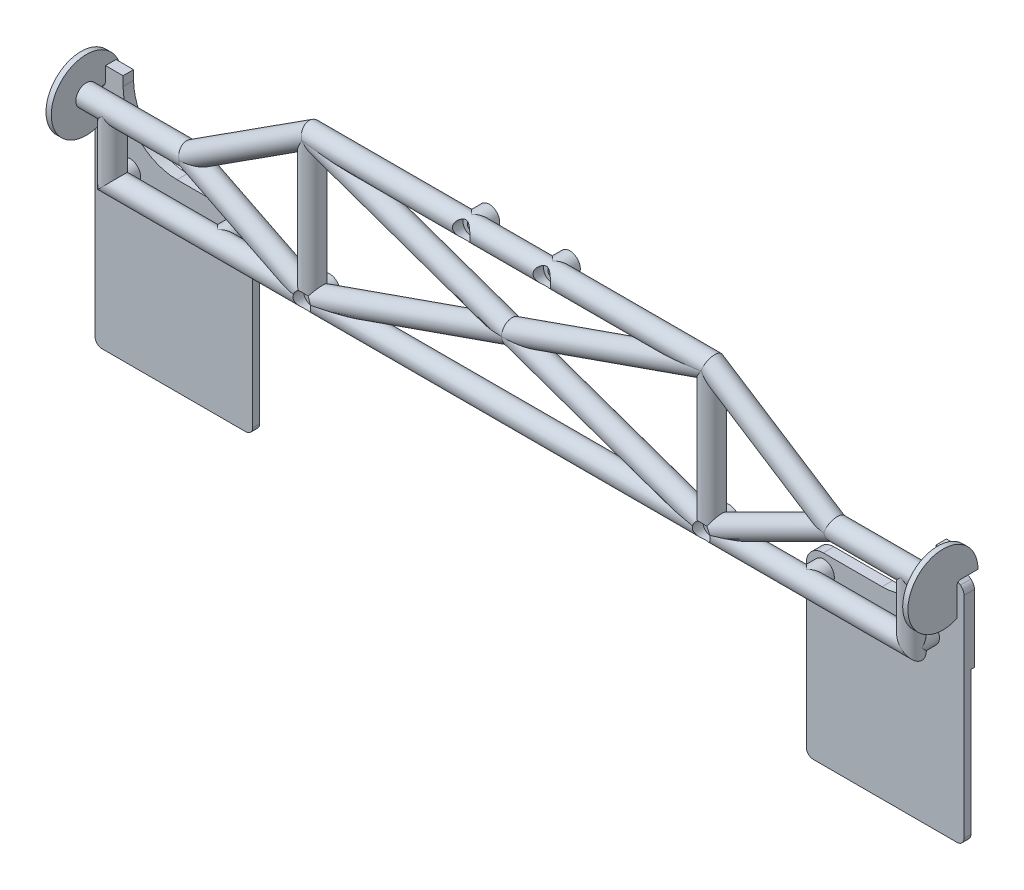
SolidWorks part; units mm, degrees
ref_plane "Front Plane" through (0, 0, 0) normal (0, 0, 1) x (1, 0, 0)
ref_plane "Top Plane" through (0, 0, 0) normal (0, 1, 0) x (1, 0, 0)
ref_plane "Right Plane" through (0, 0, 0) normal (1, 0, 0) x (0, 0, -1)
sketch "Sketch1" plane through (0, 0, 0) normal (0, 0, 1) x (1, 0, 0)
  line L0 (57, 20) -> (92, -2.5)
  line L1 (92, -2.5) -> (121.5, -2.5)
  line L2 (0, 0) -> (0, 9.1731) construction
  line L3 (57, 20) -> (-57, 20)
  line L5 (57, -20) -> (-57, 20) construction
  line L6 (57, 20) -> (-57, -20) construction
  line L7 (-92, -2.5) -> (-121.5, -2.5)
  line L8 (-57, 20) -> (-92, -2.5)
  point P0 (0, 0)
  dimension "D1" = 114
  dimension "D2" = 40
  dimension "D3" = 22.5
  dimension "D4" = 35
  dimension "D5" = 121.5
sweep "Sweep1" add path "Sketch1" circular profile diameter 6 parameters "D3"=6
sketch "Sketch108" plane through (0, 0, 0) normal (0, 0, 1) x (1, 0, 0)
  line L0 (-121.5, -2.5) -> (-92, -2.5)
  line L1 (-121.5, 0.5) -> (-121.5, -5.5) construction
  line L2 (-91.1189, -5.5) -> (-92.8811, 0.5) construction
  line L3 (-92, -2.5) -> (-57, -20)
  line L4 (-57, -20) -> (57, -20)
  line L5 (57, -20) -> (92, -2.5)
  line L6 (91.1189, -5.5) -> (92.8811, 0.5) construction
  line L7 (92, -2.5) -> (121.5, -2.5)
  line L8 (121.5, -5.5) -> (121.5, 0.5) construction
  line L9 (57, -20) -> (57, 20) construction
  line L10 (57.8811, 23) -> (56.1189, 17) construction
  line L11 (-57, 20) -> (-57, -20) construction
  line L12 (-57.8811, 23) -> (-56.1189, 17) construction
  dimension "D1" = 40
sweep "Sweep6" add path "Sketch108" circular profile diameter 6 parameters "D3"=6
sketch "Sketch121" plane through (0, 0, 0) normal (0, 0, 1) x (1, 0, 0)
  line L0 (-57, 20) -> (57, -20)
  line L1 (-57.8811, 23) -> (-56.1189, 17) construction
  line L2 (57.7082, -23) -> (56.2918, -17) construction
sweep "Sweep7" add path "Sketch121" circular profile diameter 6 parameters "D3"=6
sketch "Sketch130" plane through (0, 0, 0) normal (0, 0, 1) x (1, 0, 0)
  line L0 (-57, -20) -> (57, 20)
  line L1 (-57.7082, -23) -> (-56.2918, -17) construction
  line L2 (57.8811, 23) -> (56.1189, 17) construction
sweep "Sweep8" add path "Sketch130" circular profile diameter 6 parameters "D3"=6
sketch "Sketch143" plane through (0, 0, 0) normal (0, 0, 1) x (1, 0, 0)
  line L0 (-57, 20) -> (-57, -20)
sweep "Sweep9" add path "Sketch143" circular profile diameter 6 parameters "D3"=6
sketch "Sketch152" plane through (0, 0, 0) normal (0, 0, 1) x (1, 0, 0)
  line L0 (57, 20) -> (57, -20)
sweep "Sweep10" add path "Sketch152" circular profile diameter 6 parameters "D3"=6
sketch "Sketch165" plane through (0, 0, 0) normal (0, 0, 1) x (1, 0, 0)
  line L0 (57, -20) -> (114, -20)
  line L1 (114, -20) -> (114, -2.5)
  line L2 (121.5, -2.5) -> (116.1969, -2.5) construction
  line L3 (121.5, -5.5) -> (121.5, 0.5) construction
  dimension "D1" = 57
sweep "Sweep11" add path "Sketch165" circular profile diameter 6 parameters "D3"=6
mirror "Mirror1" about plane through (0, 0, 0) normal (1, 0, 0) of "Sweep11"
sketch "Sketch182" plane through (0, 0, 0) normal (0, 0, 1) x (1, 0, 0)
  line L0 (-8.5, 20) -> (8.5, 20) construction
  line L1 (0, 20) -> (0, 0) construction
  line L2 (117, -23) -> (111, -17) construction
  line L3 (114, -20) -> (111.8989, -20) construction
  line L4 (-117, -23) -> (-111, -17) construction
  line L5 (-114, -20) -> (-111.7577, -20) construction
  circle A0 centre (11.5, 20) radius 3
  circle A1 centre (-11.5, 20) radius 3
  circle A2 centre (57, -20) radius 3
  circle A3 centre (-57, -20) radius 3
  circle A4 centre (114, -20) radius 3
  circle A5 centre (84, -20) radius 3
  circle A6 centre (-114, -20) radius 3
  circle A7 centre (-84, -20) radius 3
  dimension "D2" = 6
  dimension "D3" = 6
  dimension "D4" = 6
  dimension "D5" = 6
  dimension "D6" = 6
  dimension "D7" = 6
  dimension "D9" = 6
  dimension "D10" = 6
  dimension "D1" = 17
  dimension "D8" = 30
  dimension "D11" = 30
extrude "Boss-Extrude1" add sketch "Sketch182" against normal blind 5
sketch "Sketch183" plane through (0, 0, 0) normal (0, 0, 1) x (1, 0, 0)
  circle A0 centre (11.5, 20) radius 2.5
  circle A1 centre (-11.5, 20) radius 2.5
  circle A2 centre (57, -20) radius 2.5
  circle A3 centre (-57, -20) radius 2.5
  circle A4 centre (-57, -20) radius 3 construction
  circle A6 centre (-11.5, 20) radius 3 construction
  circle A7 centre (11.5, 20) radius 3 construction
  circle A8 centre (57, -20) radius 3 construction
  dimension "D1" = 5
  dimension "D2" = 5
  dimension "D3" = 5
  dimension "D4" = 5
extrude "Cut-Extrude1" cut sketch "Sketch183" along normal blind 5
sketch "Sketch184" plane through (0, 0, -5) normal (0, 0, -1) x (-1, 0, 0)
  circle A0 centre (-11.5, 20) radius 1.25
  circle A1 centre (11.5, 20) radius 1.25
  circle A2 centre (57, -20) radius 1.25
  circle A3 centre (-57, -20) radius 1.25
  dimension "D1" = 2.5
  dimension "D2" = 2.5
  dimension "D3" = 2.5
  dimension "D4" = 2.5
extrude "Cut-Extrude2" cut sketch "Sketch184" against normal through all
ref_axis "Axis1" through (-11.5, 20, 0) along (0, 0, -1)
ref_axis "Axis2" through (11.5, 20, 0) along (0, 0, -1)
ref_plane "Plane1" through (0, 20, 0) normal (0, -1, 0) x (-1, 0, 0)
sketch "Sketch201" plane through (121.5, 0, 0) normal (1, 0, 0) x (0, 0, -1)
  line L0 (10, -2.5) -> (5, -2.5)
  line L1 (4, -3.5) -> (4, -11.6652)
  circle A0 centre (0, -2.5) radius 10
  circle A1 centre (0, -2.5) radius 3 construction
  arc A2 (4, -3.5) -> (5, -2.5) centre (5, -3.5) cw
  point P9 (4, -2.5)
  circle M2 centre (0, -2.5) radius 3
  dimension "D1" = 20
  dimension "D3" = 1
  dimension "D2" = 6
extrude "Boss-Extrude2" add sketch "Sketch201" along normal blind 1.5 separate body contours L1 A2 L0 A0 M2 | M2 region at (121.5, -2.2172, -7.5) region at (121.5, -2.5, 0)
mirror "Mirror3" about plane through (0, 0, 0) normal (1, 0, 0) of "Boss-Extrude2"
sketch "Sketch202" plane through (0, 0, -5) normal (0, 0, -1) x (-1, 0, 0)
  line L0 (124, -66) -> (124, -5.9498)
  line L1 (123, -3.5) -> (123, -11.6652) construction
  line L2 (122.967, -3.9255) -> (122.033, -3.2486)
  line L3 (121, -1.2243) -> (121, 2.5)
  line L4 (121, 2.5) -> (116, 2.5)
  line L5 (116, 2.5) -> (116, -0.1131)
  line L6 (100.6131, -15.5) -> (83.865, -15.5)
  line L7 (79, -20.365) -> (79, -66)
  line L8 (122, -68) -> (81, -68)
  line L9 (111, -17) -> (84, -17) construction
  arc A0 (116, -0.1131) -> (100.6131, -15.5) centre (100.6131, -0.1131) cw
  arc A1 (83.865, -15.5) -> (79, -20.365) centre (83.865, -20.365) ccw
  arc A2 (122.967, -3.9255) -> (124, -5.9498) centre (121.5, -5.9498) cw
  arc A3 (122.033, -3.2486) -> (121, -1.2243) centre (123.5, -1.2243) cw
  arc A4 (124, -66) -> (122, -68) centre (122, -66) cw
  arc A5 (81, -68) -> (79, -66) centre (81, -66) cw
  point P13 (80.2038, -64.3084)
  point P17 (124, -4.6741)
  point P22 (121, -2.5)
  point P23 (116, -0.1131)
  point P24 (83.865, -15.5)
  dimension "D9" = 2.5
  dimension "D10" = 2
  dimension "D1" = 1
  dimension "D2" = 45
  dimension "D3" = 52.5
  dimension "D4" = 18
  dimension "D5" = 1.5
  dimension "D6" = 3
  dimension "D7" = 5
  dimension "D8" = 5
extrude "Boss-Extrude3" add sketch "Sketch202" along normal blind 3 contours L7 A5 L8 A4 L0 A2 L2 A3 L3 L4 L5 A0 L6 A1
sketch "Sketch203" plane through (0, 0, -8) normal (0, 0, -1) x (-1, 0, 0)
  line L0 (83.865, -25.2301) -> (114, -25.2301) construction
  line L1 (87.3786, -23.7301) -> (110.3339, -23.7301)
  line L2 (114, -25.2301) -> (124, -25.2301)
  line L3 (124, -66) -> (124, -5.9498) construction
  line L5 (120.5693, -6.6241) -> (118.9564, -5.8653)
  line L6 (121, -66) -> (121, -5.9498)
  line L7 (121, -66) -> (121, -7.3027)
  line L20 (124, -66) -> (124, -5.9498)
  line L21 (81, -68) -> (122, -68)
  line L22 (79, -20.365) -> (79, -66)
  line L23 (124, -66) -> (124, -5.9498)
  line L24 (81, -68) -> (122, -68)
  line L25 (79, -20.365) -> (79, -66)
  circle A0 centre (83.865, -20.365) radius 4.865
  arc A1 (83.865, -15.5) -> (79, -20.365) centre (83.865, -20.365) ccw construction
  circle A2 centre (114, -20) radius 5.2301
  circle A4 centre (114, -20) radius 3 construction
  arc A5 (118.9212, -18.2294) -> (121, -17.8668) centre (119.929, -17.8668) ccw
  arc A6 (100.6131, -18.5) -> (119, -0.1131) centre (100.6131, -0.1131) ccw
  arc A7 (100.6131, -18.5) -> (117.9307, -6.292) centre (100.6131, -0.1131) ccw
  arc A8 (109.3093, -16.3136) -> (109.8006, -16.8824) centre (109.4914, -16.6529) ccw
  arc A9 (121, -7.3027) -> (120.5693, -6.6241) centre (120.25, -7.3027) ccw
  arc A10 (118.9564, -5.8653) -> (117.9307, -6.292) centre (118.6371, -6.544) ccw
  arc A19 (122, -68) -> (124, -66) centre (122, -66) ccw
  arc A20 (79, -66) -> (81, -68) centre (81, -66) ccw
  arc A21 (122, -68) -> (124, -66) centre (122, -66) ccw
  arc A22 (79, -66) -> (81, -68) centre (81, -66) ccw
  point P26 (109.3093, -16.6529)
  line M11 (79, -20.365) -> (79, -66)
  arc M12 (79, -66) -> (81, -68) centre (81, -66) ccw
  line M13 (81, -68) -> (122, -68)
  arc M14 (122, -68) -> (124, -66) centre (122, -66) ccw
  line M15 (124, -66) -> (124, -5.9498)
  dimension "D4" = 0.75
  dimension "D1" = 3
  dimension "D2" = 3
  dimension "D3" = 3
  dimension "D5" = 0
extrude "Cut-Extrude3" cut sketch "Sketch203" against normal blind 1 contours L0 A0 L2 M11 M12 M13 M14 M15 | L5 A10 A7 A8 A2 A5 L7 A9 region at (-101.4436, -46.5372, -8) region at (-117.9723, -12.4684, -8)
mirror "Mirror4" about plane through (0, 0, 0) normal (1, 0, 0) of "Cut-Extrude3", "Boss-Extrude3"
